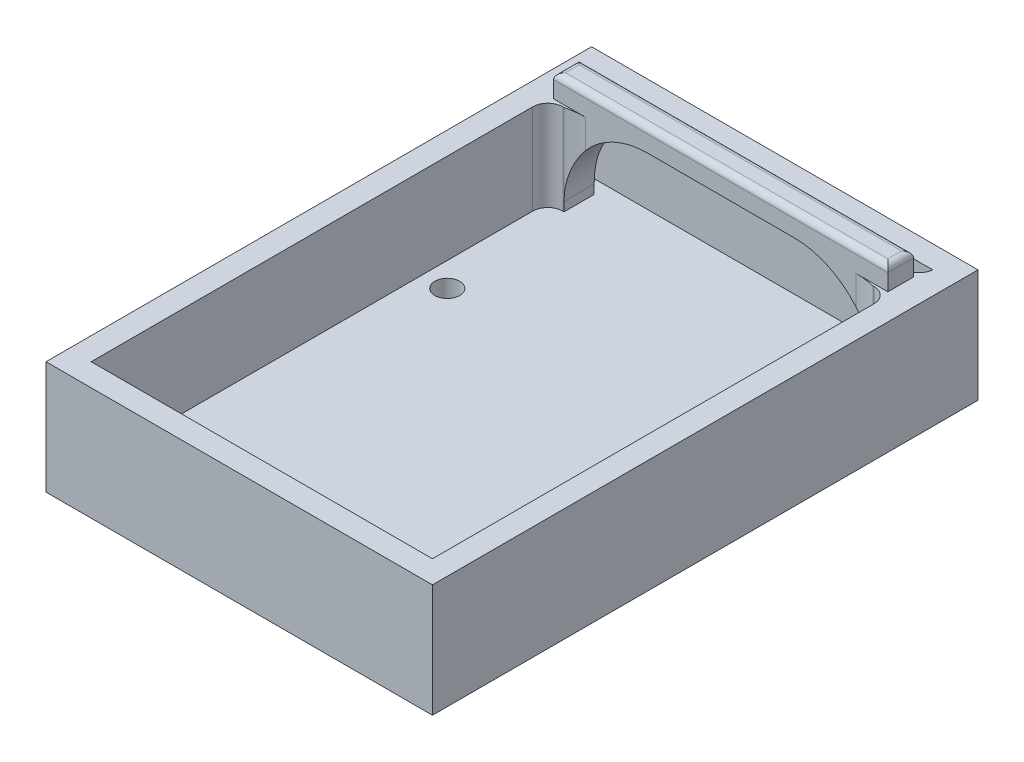
SolidWorks part; units mm, degrees
ref_plane "Front Plane" through (0, 0, 0) normal (0, 0, 1) x (1, 0, 0)
ref_plane "Top Plane" through (0, 0, 0) normal (0, 1, 0) x (1, 0, 0)
ref_plane "Right Plane" through (0, 0, 0) normal (1, 0, 0) x (0, 0, -1)
sketch "Sketch1" plane through (0, 0, 0) normal (0, 1, 0) x (1, 0, 0)
  line L0 (-51.7792, 52.1024) -> (-6.7792, 52.1024)
  line L1 (-51.7792, 56.1024) -> (-51.7792, 52.1024)
  line L2 (-6.7792, 56.1024) -> (-51.7792, 56.1024)
  line L3 (-6.7792, 52.1024) -> (-6.7792, 56.1024)
  line L4 (-8.4825, 47.0305) -> (-38.4825, 47.0305)
  line L5 (-8.4825, 41.0305) -> (-8.4825, 47.0305)
  line L6 (-38.4825, 41.0305) -> (-8.4825, 41.0305)
  line L7 (-38.4825, 47.0305) -> (-38.4825, 41.0305)
  line L8 (-3.6192, 60.9146) -> (-54.9392, 60.9146)
  line L9 (-54.9392, 60.9146) -> (-54.9392, -11.5354)
  line L10 (-54.9392, -11.5354) -> (-3.6192, -11.5354)
  line L11 (-3.6192, -11.5354) -> (-3.6192, 60.9146)
  line L12 (-3.6192, 60.9146) -> (-3.6192, -11.5354)
  line L13 (-54.9392, -11.5354) -> (-54.9392, 60.9146)
  line L14 (-54.9392, 60.9146) -> (-3.6192, 60.9146)
  line L15 (-3.6192, -14.8687) -> (-3.6192, -11.5354)
  line L16 (-3.6192, -11.5354) -> (-54.9392, -11.5354)
  line L17 (-54.9392, -11.5354) -> (-54.9392, -14.8687)
  line L18 (-48.7292, 37.1946) -> (-9.8292, 37.1946)
  line L19 (-8.1792, -5.5354) -> (-8.1792, 35.5446)
  line L20 (-50.3792, 35.5446) -> (-50.3792, -5.5354)
  line L21 (-48.7292, -7.1854) -> (-9.8292, -7.1854)
  line L22 (-51.9392, 39.1946) -> (-51.9392, -3.8854)
  line L23 (-6.6192, -8.5354) -> (-6.6192, 39.1946)
  line L24 (-51.9392, -8.5354) -> (-6.6192, -8.5354)
  line L25 (-51.9392, -1.6922) -> (-51.9392, -8.5354)
  line L26 (-51.9392, 39.1946) -> (-6.6192, 39.1946)
  line L27 (-51.9392, 39.1946) -> (-51.9392, 57.9146)
  line L28 (-51.9392, 57.9146) -> (-6.6192, 57.9146)
  line L29 (-6.6192, 57.9146) -> (-6.6192, 39.1946)
  circle A0 centre (-48.7292, 35.5446) radius 1.65
  circle A1 centre (-9.8292, 35.5446) radius 1.65
  circle A2 centre (-9.8292, -5.5354) radius 1.65
  circle A3 centre (-48.7292, -5.5354) radius 1.65
  dimension "D1" = 2
  dimension "D2" = 3
  dimension "D3" = 3
  dimension "D4" = 3
  dimension "D5" = 3
extrude "Boss-Extrude1" add sketch "Sketch1" against normal blind 3 contours L9 L10 L11 L8
extrude "Boss-Extrude2" add sketch "Sketch1<3>" along normal blind 12 contours L10 L11 L8 L9 L28 L29 L23 L24 L25 L22 L27 region at (-4.507, 0, -24.6896)
sketch "Sketch1<3>" plane through (0, 0, 0) normal (0, 1, 0) x (1, 0, 0) same geometry as "Sketch1"
extrude "Boss-Extrude3" add sketch "Sketch1<4>" along normal blind 3 from surface separate body contours L0 L3 L2 L1 region at (-29.2792, 0, -54.1024) starting at face at (-29.2792, 12, -24.6896)
sketch "Sketch1<4>" plane through (0, 0, 0) normal (0, 1, 0) x (1, 0, 0) same geometry as "Sketch1"
sketch "Sketch3" plane through (0, 0, 0) normal (0, 1, 0) x (1, 0, 0)
  line L0 (-51.7792, 56.1024) -> (-51.7792, 52.1024) construction
  line L1 (-53.7792, 52.1024) -> (-49.7792, 52.1024)
  line L2 (-53.7792, 52.1024) -> (-53.7792, 56.1024)
  line L3 (-53.7792, 56.1024) -> (-49.7792, 56.1024)
  line L4 (-49.7792, 52.1024) -> (-49.7792, 56.1024)
  line L5 (-53.7792, 52.1024) -> (-49.7792, 56.1024) construction
  line L6 (-53.7792, 56.1024) -> (-49.7792, 52.1024) construction
  line L7 (-6.7792, 56.1024) -> (-51.7792, 56.1024) construction
  line L8 (-6.7792, 52.1024) -> (-6.7792, 56.1024) construction
  line L9 (-4.7792, 52.1024) -> (-8.7792, 52.1024)
  line L10 (-4.7792, 52.1024) -> (-4.7792, 56.1024)
  line L11 (-4.7792, 56.1024) -> (-8.7792, 56.1024)
  line L12 (-8.7792, 52.1024) -> (-8.7792, 56.1024)
  line L13 (-4.7792, 52.1024) -> (-8.7792, 56.1024) construction
  line L14 (-4.7792, 56.1024) -> (-8.7792, 52.1024) construction
  point P0 (-51.7792, 54.1024)
  point P9 (-6.7792, 54.1024)
  dimension "D1" = 4
  dimension "D2" = 4
extrude "Boss-Extrude4" add sketch "Sketch3" along normal up to surface (12 mm away) up to face at (-29.2792, 12, -24.6896)
fillet "Fillet2" radius 2 4 edges at (-6.6192, 6, -52.1024) (-6.6192, 6, -56.1024) (-51.9392, 6, -56.1024) (-51.9392, 6, -52.1024)
sketch "Sketch4" plane through (0, 15, 0) normal (0, 1, 0) x (1, 0, 0)
  line L0 (-8.6103, 55.8024) -> (-49.948, 55.8024)
  line L1 (-51.4792, 55.8024) -> (-51.4792, 52.4024)
  line L2 (-49.9392, 52.4024) -> (-8.6192, 52.4024)
  line L3 (-7.0792, 52.4024) -> (-7.0792, 55.8024)
  line L4 (-8.6103, 56.1024) -> (-49.948, 56.1024)
  line L5 (-51.7792, 57.2981) -> (-51.7792, 50.8862)
  line L6 (-49.9392, 52.1024) -> (-8.6192, 52.1024)
  line L7 (-6.7792, 50.8862) -> (-6.7792, 57.2981)
  line L8 (-8.6103, 56.1024) -> (-49.948, 56.1024)
  line L9 (-51.7792, 57.2981) -> (-51.7792, 50.8862)
  line L10 (-49.9392, 52.1024) -> (-8.6192, 52.1024)
  line L11 (-6.7792, 50.8862) -> (-6.7792, 57.2981)
  line L12 (-49.948, 55.8024) -> (-51.4792, 55.8024)
  line L13 (-49.9392, 52.4024) -> (-51.4792, 52.4024)
  line L14 (-8.6103, 55.8024) -> (-7.0792, 55.8024)
  line L15 (-8.6192, 52.4024) -> (-7.0792, 52.4024)
  line L16 (-7.0792, 51.8107) -> (-7.0792, 56.3861) construction
  line L17 (-51.7792, 57.2981) -> (-51.4792, 58.8234)
  line L18 (-51.4792, 56.3861) -> (-51.4792, 51.8107) construction
  line L19 (-51.4792, 58.8234) -> (-53.9865, 56.1024)
  line L20 (-53.9865, 56.1024) -> (-52.2397, 50.1024)
  line L21 (-52.2397, 50.1024) -> (-52.0975, 48.7287)
  line L22 (-52.0975, 48.7287) -> (-51.7792, 50.8862)
  line L23 (-6.7792, 57.2981) -> (-6.937, 58.8234)
  line L24 (-6.937, 58.8234) -> (-4.8722, 58.6529)
  line L25 (-4.8722, 58.6529) -> (-5.9046, 53.404)
  line L26 (-5.9046, 53.404) -> (-6.2015, 49.8074)
  line L27 (-6.2015, 49.8074) -> (-7.0792, 49.8074)
  line L28 (-7.0792, 49.8074) -> (-6.7792, 50.8862)
  arc A4 (-51.7792, 57.2981) -> (-49.948, 56.1024) centre (-49.948, 58.1024) ccw
  arc A5 (-49.9392, 52.1024) -> (-51.7792, 50.8862) centre (-49.9392, 50.1024) ccw
  arc A6 (-6.7792, 50.8862) -> (-8.6192, 52.1024) centre (-8.6192, 50.1024) ccw
  arc A7 (-8.6103, 56.1024) -> (-6.7792, 57.2981) centre (-8.6103, 58.1024) ccw
  arc A8 (-51.7792, 57.2981) -> (-49.948, 56.1024) centre (-49.948, 58.1024) ccw
  arc A9 (-49.9392, 52.1024) -> (-51.7792, 50.8862) centre (-49.9392, 50.1024) ccw
  arc A10 (-6.7792, 50.8862) -> (-8.6192, 52.1024) centre (-8.6192, 50.1024) ccw
  arc A11 (-8.6103, 56.1024) -> (-6.7792, 57.2981) centre (-8.6103, 58.1024) ccw
  arc A12 (-8.6103, 55.8024) -> (-7.0792, 56.3861) centre (-8.6103, 58.1024) ccw construction
  arc A13 (-7.0792, 51.8107) -> (-8.6192, 52.4024) centre (-8.6192, 50.1024) ccw construction
  arc A14 (-51.4792, 56.3861) -> (-49.948, 55.8024) centre (-49.948, 58.1024) ccw construction
  arc A15 (-49.9392, 52.4024) -> (-51.4792, 51.8107) centre (-49.9392, 50.1024) ccw construction
  line M17 (-8.6103, 56.1024) -> (-49.948, 56.1024)
  arc M18 (-49.948, 56.1024) -> (-51.7792, 57.2981) centre (-49.948, 58.1024) cw
  line M19 (-51.7792, 57.2981) -> (-51.7792, 50.8862)
  arc M20 (-51.7792, 50.8862) -> (-49.9392, 52.1024) centre (-49.9392, 50.1024) cw
  line M21 (-49.9392, 52.1024) -> (-8.6192, 52.1024)
  arc M22 (-8.6192, 52.1024) -> (-6.7792, 50.8862) centre (-8.6192, 50.1024) cw
  line M23 (-6.7792, 50.8862) -> (-6.7792, 57.2981)
  arc M24 (-6.7792, 57.2981) -> (-8.6103, 56.1024) centre (-8.6103, 58.1024) cw
  dimension "D1" = 0
  dimension "D2" = 0.3
extrude "Cut-Extrude1" cut sketch "Sketch4" against normal up to surface (3 mm away) contours L15 L2 L13 L1 L12 L0 L14 L3 M24 M17 M18 M19 M20 M21 M22 M23 | L28 L27 L26 L25 L24 L23 M23 | L21 L22 L17 L19 L20 M19 region at (-7.2683, 15, -56.0472) region at (-6.1658, 15, -55.1453) region at (-52.514, 15, -54.5096) up to face at (-29.2792, 12, -41.5335)
fillet "Fillet3" radius 0.8 4 edges at (-51.4792, 15, -54.1024) (-7.0792, 15, -54.1024) (-29.2792, 15, -52.4024) (-29.2792, 15, -55.8024)
extrude "Cut-Extrude2" cut sketch "Sketch1<5>" against normal through all both and the other way through all contours A1 | A0 | A3 | A2
sketch "Sketch1<5>" plane through (0, 0, 0) normal (0, 1, 0) x (1, 0, 0) same geometry as "Sketch1"
fillet "Fillet4" radius 10.8 2 edges at (-8.7792, 12, -54.1024) (-49.7792, 12, -54.1024)
fillet "Fillet5" radius 10.8 2 edges at (-8.7792, 6.6, -52.4024) (-49.7792, 6.6, -52.4024)
fillet "Fillet6" radius 10.8 2 edges at (-49.7792, 6.6, -55.8024) (-8.7792, 6.6, -55.8024)
